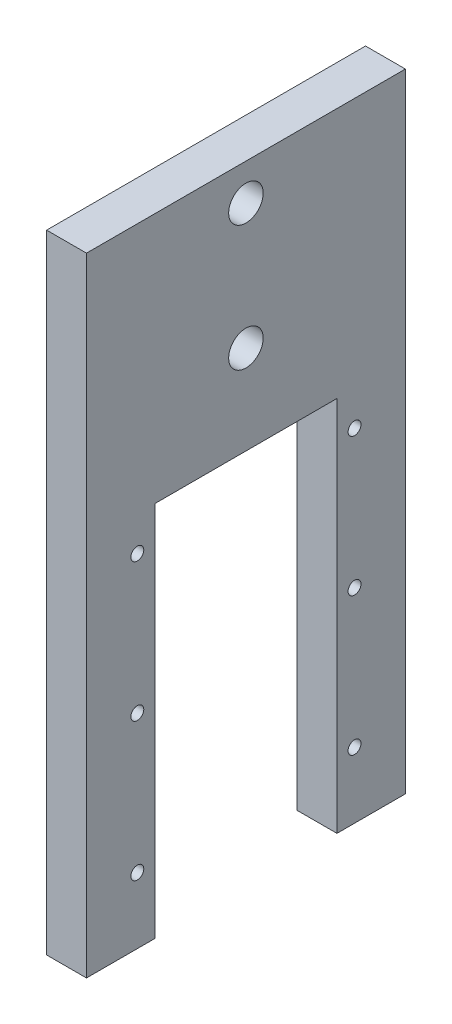
SolidWorks part; units mm, degrees
ref_plane "Front Plane" through (0, 0, 0) normal (0, 0, 1) x (1, 0, 0)
ref_plane "Top Plane" through (0, 0, 0) normal (0, 1, 0) x (1, 0, 0)
ref_plane "Right Plane" through (0, 0, 0) normal (1, 0, 0) x (0, 0, -1)
sketch "Sketch2" plane through (0, 0, 0) normal (0, 0, 1) x (1, 0, 0)
  line L1 (3.175, -50) -> (-3.175, -50)
  line L2 (3.175, -50) -> (3.175, 50)
  line L3 (3.175, 50) -> (-3.175, 50)
  line L4 (-3.175, -50) -> (-3.175, 50)
  line L5 (3.175, -50) -> (-3.175, 50) construction
  line L6 (3.175, 50) -> (-3.175, -50) construction
  point P0 (0, 0)
  dimension "D1" = 100
  dimension "D2" = 6.35
extrude "Boss-Extrude1" add sketch "Sketch2" along normal mid plane 50.8
sketch "Sketch4" plane through (-3.175, 0, 0) normal (-1, 0, 0) x (0, 0, 1)
  line L0 (14.5, -50) -> (14.5, 10)
  line L2 (14.5, 10) -> (-14.5, 10)
  line L3 (0, 0.0539) -> (0, 22.3365) construction
  line L4 (-14.5, -50) -> (-14.5, 10)
  line L5 (-14.5, -50) -> (14.5, -50)
  line L6 (25.4, -50) -> (-25.4, -50) construction
  line L8 (17.3, -39.5) -> (17.3, -17.5) construction
  line L9 (17.3, -17.5) -> (17.3, 4.5) construction
  circle A0 centre (17.3, -39.5) radius 1.025
  circle A1 centre (-17.3, -39.5) radius 1.025
  circle A2 centre (17.3, -17.5) radius 1.025
  circle A3 centre (-17.3, -17.5) radius 1.025
  circle A4 centre (-17.3, 4.5) radius 1.025
  circle A5 centre (17.3, 4.5) radius 1.025
  point P8 (0, 10)
  dimension "D5" = 2.05
  dimension "D1" = 60
  dimension "D2" = 29
  dimension "D3" = 10.5
  dimension "D4" = 2.8
  dimension "D6" = 22
extrude "Cut-Extrude4" cut sketch "Sketch4" against normal through all contours L0 L2 L4 L5 | A0 | A2 | A5 | A1 | A3 | A4
hole_wizard "M5 Clearance Hole1" positions "Sketch7" profile "Sketch6" hole size "M5" standard "ANSI Metric" end condition up to next
sketch "Sketch7" plane through (-3.175, 0, 0) normal (-1, 0, 0) x (0, 0, 1)
  line L1 (25.4, 50) -> (-25.4, 50) construction
  line L2 (14.5, 10) -> (14.5, 50) construction
  line L4 (14.5, 34.2068) -> (-12.8341, 34.2068) construction
  point P0 (0, 44.2068)
  point P2 (0, 24.2068)
  dimension "D1" = 20
sketch "Sketch6" plane through (-3.175, 44.2068, 0) normal (0, 1, 0) x (0, 0, 1)
  line L0 (0, 0) -> (0, 6.35)
  line L1 (0, 6.35) -> (2.75, 6.35)
  line L2 (2.75, 6.35) -> (2.75, 0)
  line L5 (2.75, 0) -> (0, 0)
  line L11 (0, -6.35) -> (0, 107.95) construction
  dimension "Thru Hole Dia." = 5.5
  dimension "Thru Hole Depth" = 6.35
